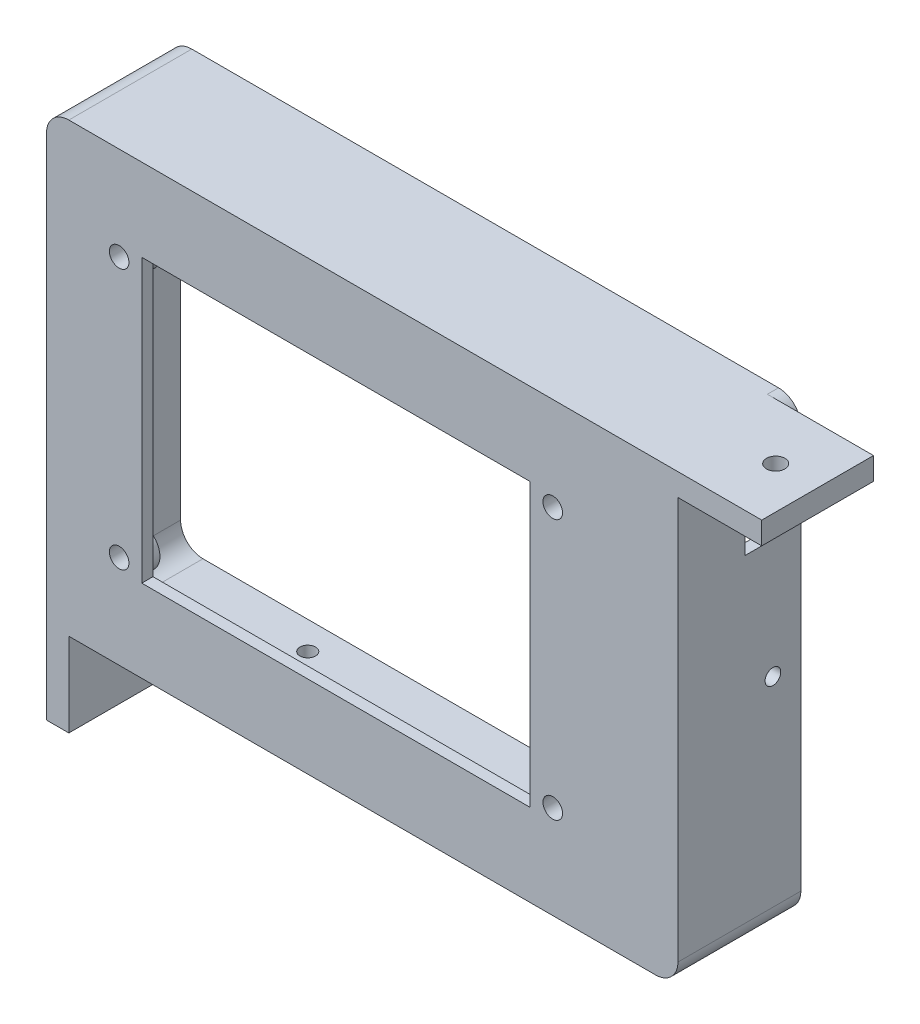
SolidWorks part; units mm, degrees
ref_plane "前视基准面" through (0, 0, 0) normal (0, 0, 1) x (1, 0, 0)
ref_plane "上视基准面" through (0, 0, 0) normal (0, 1, 0) x (1, 0, 0)
ref_plane "右视基准面" through (0, 0, 0) normal (1, 0, 0) x (0, 0, -1)
sketch "草图1" plane through (0, 0, 0) normal (0, 0, 1) x (1, 0, 0)
  line L1 (0, 0) -> (69.5, 0)
  line L2 (0, 0) -> (0, 50.5)
  line L3 (0, 50.5) -> (69.5, 50.5)
  line L4 (69.5, 0) -> (69.5, 50.5)
  line L5 (-17.05, 65.25) -> (95.95, 65.25)
  line L6 (-17.05, 65.25) -> (-17.05, -14.75)
  line L7 (-17.05, -14.75) -> (95.95, -14.75)
  line L8 (95.95, 65.25) -> (95.95, -14.75)
  circle A0 centre (-4.05, 48.55) radius 1.75
  circle A1 centre (73.55, 48.55) radius 1.75
  circle A2 centre (73.55, 1.95) radius 1.75
  circle A3 centre (-4.05, 1.95) radius 1.75
  point P10 (-17.05, 25.25)
  point P11 (0, 25.25)
  point P13 (34.75, 50.5)
  point P21 (69.5, 25.25)
  dimension "D9" = 3.5
  dimension "D1" = 50.5
  dimension "D2" = 69.5
  dimension "D3" = 113
  dimension "D4" = 80
  dimension "D5" = 46.6
  dimension "D6" = 77.6
  dimension "D7" = 38.8
  dimension "D8" = 23.3
  dimension "D10" = 13
extrude "凸台-拉伸1" add sketch "草图1" along normal blind 2
sketch "草图2" plane through (0, 0, 0) normal (0, 0, -1) x (-1, 0, 0)
  circle A0 centre (-73.55, 48.55) radius 3.5
  circle A1 centre (4.05, 48.55) radius 3.5
  circle A2 centre (4.05, 1.95) radius 3.5
  circle A3 centre (-73.55, 1.95) radius 3.5
  circle A5 centre (-73.55, 48.55) radius 1.75 construction
  circle A6 centre (4.05, 48.55) radius 1.75 construction
  circle A7 centre (4.05, 1.95) radius 1.75 construction
  circle A8 centre (-73.55, 1.95) radius 1.75 construction
  circle A9 centre (-73.55, 48.55) radius 1.75
  circle A10 centre (4.05, 48.55) radius 1.75
  circle A11 centre (4.05, 1.95) radius 1.75
  circle A12 centre (-73.55, 1.95) radius 1.75
  dimension "D1" = 7
extrude "凸台-拉伸2" add sketch "草图2" along normal blind 1.8
sketch "草图4" plane through (0, 0, 0) normal (0, 0, -1) x (-1, 0, 0)
  line L1 (-93.95, 63.25) -> (15.05, 63.25)
  line L2 (-93.95, 63.25) -> (-93.95, -12.75)
  line L3 (-93.95, -12.75) -> (15.05, -12.75)
  line L4 (17.05, -14.75) -> (17.05, 65.25)
  line L5 (17.05, 65.25) -> (-95.95, 65.25)
  line L6 (-95.95, 65.25) -> (-95.95, -14.75)
  line L7 (-95.95, -14.75) -> (17.05, -14.75)
  line L8 (17.05, -14.75) -> (17.05, 65.25)
  line L9 (17.05, 65.25) -> (-95.95, 65.25)
  line L10 (-95.95, 65.25) -> (-95.95, -14.75)
  line L11 (-95.95, -14.75) -> (17.05, -14.75)
  line L12 (15.05, 63.25) -> (15.05, -12.75)
  dimension "D2" = 2
  dimension "D3" = 2
  dimension "D4" = 2
  dimension "D5" = 2
  dimension "D1" = 0
extrude "凸台-拉伸3" add sketch "草图4" along normal blind 20
fillet "圆角1" radius 4 8 edges at (93.95, -12.75, -10) (93.95, 63.25, -10) (-15.05, 63.25, -10) (-15.05, -12.75, -10) (-17.05, 65.25, -9) (-17.05, -14.75, -9) (95.95, -14.75, -9) (95.95, 65.25, -9)
sketch "草图5" plane through (95.95, 0, 0) normal (1, 0, 0) x (0, 0, -1)
  line L0 (20, 61.25) -> (20, -10.75) construction
  line L1 (20, 61.25) -> (10, 61.25)
  line L2 (20, 61.25) -> (20, 46.25)
  line L3 (20, 46.25) -> (10, 46.25)
  line L4 (10, 61.25) -> (10, 46.25)
  line L5 (-2, 65.25) -> (20, 65.25) construction
  dimension "D1" = 15
  dimension "D2" = 4
  dimension "D3" = 10
extrude "切除-拉伸1" cut sketch "草图5" against normal blind 20
sketch "草图6" plane through (0, 0, 2) normal (0, 0, 1) x (1, 0, 0)
  line L0 (-17.05, -10.75) -> (-17.05, -29.75)
  line L1 (-17.05, -29.75) -> (-13.05, -29.75)
  line L2 (-13.05, -29.75) -> (-13.05, -14.75)
  line L3 (91.95, 65.25) -> (110.95, 65.25)
  line L4 (110.95, 65.25) -> (110.95, 61.25)
  line L5 (110.95, 61.25) -> (95.95, 61.25)
  arc A0 (-17.05, -10.75) -> (-13.05, -14.75) centre (-13.05, -10.75) ccw construction
  arc A1 (95.95, 61.25) -> (91.95, 65.25) centre (91.95, 61.25) ccw construction
  arc A2 (-17.05, -10.75) -> (-13.05, -14.75) centre (-13.05, -10.75) ccw
  arc A3 (95.95, 61.25) -> (91.95, 65.25) centre (91.95, 61.25) ccw
  dimension "D1" = 15
  dimension "D2" = 15
extrude "凸台-拉伸4" add sketch "草图6" against normal blind 20
sketch "草图7" plane through (-13.05, 0, 0) normal (1, 0, 0) x (0, 0, -1)
  circle A0 centre (8, -22.25) radius 1.65
  dimension "D1" = 3.3
extrude "切除-拉伸2" cut sketch "草图7" against normal blind 20
sketch "草图8" plane through (0, 61.25, 0) normal (0, -1, 0) x (1, 0, 0)
  circle A0 centre (103.45, -8) radius 1.65
  dimension "D1" = 3.3
extrude "切除-拉伸3" cut sketch "草图8" against normal blind 20
sketch "草图9" plane through (95.95, 0, 0) normal (1, 0, 0) x (0, 0, -1)
  circle A0 centre (15, 25) radius 1.4
  dimension "D1" = 2.8
extrude "切除-拉伸4" cut sketch "草图9" against normal blind 10
sketch "草图10" plane through (0, -14.75, 0) normal (0, -1, 0) x (1, 0, 0)
  circle A0 centre (12.7, -15) radius 1.4
  circle A1 centre (66.2, -15) radius 1.4
  dimension "D1" = 2.8
  dimension "D2" = 2.8
extrude "切除-拉伸5" cut sketch "草图10" against normal blind 10
